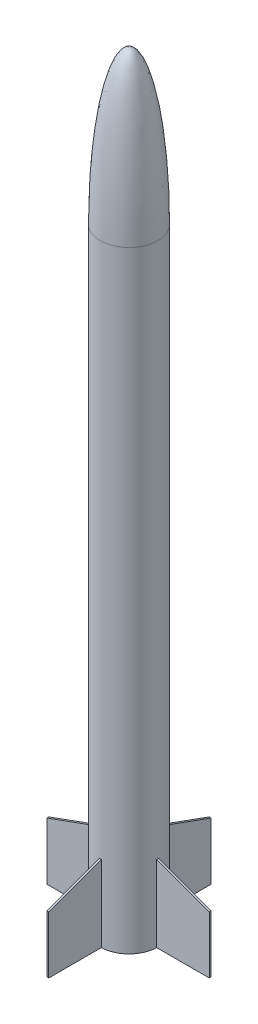
SolidWorks part; units mm, degrees
ref_plane "Front Plane" through (0, 0, 0) normal (0, 0, 1) x (1, 0, 0)
ref_plane "Top Plane" through (0, 0, 0) normal (0, 1, 0) x (1, 0, 0)
ref_plane "Right Plane" through (0, 0, 0) normal (1, 0, 0) x (0, 0, -1)
sketch "Sketch1" plane through (0, 0, 0) normal (0, 0, 1) x (1, 0, 0)
  line L0 (75, 0) -> (75, 1600)
  line L1 (0, 0) -> (0, 2000) construction
  line L2 (65, 0) -> (65, 1600)
  line L3 (0, 1990) -> (0, 2000)
  line L4 (65, 0) -> (75, 0)
  ellipse E0 centre (0, 1600) end of major axis (0, 2000) minor radius 75 (75, 1600) -> (0, 2000) ccw
  spline S0 degree 1 poles (65, 1600) (0, 1990) knots 0 0 1 1 construction
  spline S1 degree 3 poles (65, 1600) (65, 1613.008) (64.76, 1639.0954) (63.6835, 1677.7875) (61.9012, 1715.7351) (58.6084, 1764.8191) (52.8332, 1822.4383) (45.0808, 1872.7908) (37.9007, 1907.4884) (32.0956, 1930.4423) (25.9549, 1950.0586) (19.5957, 1966.0734) (13.2092, 1978.2156) (8.1667, 1984.8479) (4.7233, 1987.9953) (2.6031, 1989.3526) (1.3254, 1989.8256) (0.5303, 1989.9775) (0.1812, 1990) (0, 1990) knots -1.570796 -1.570796 -1.570796 -1.570796 -1.472622 -1.374447 -1.276272 -1.178097 -0.981748 -0.785398 -0.687223 -0.589049 -0.490874 -0.392699 -0.294524 -0.19635 -0.147262 -0.098175 -0.049087 -0.024544 0 0 0 0
  dimension "D1" = 75
  dimension "D2" = 1600
  dimension "D3" = 2000
  dimension "D4" = 10
revolve "Body & Nose cone" add sketch "Sketch1" angle 360 about L1
sketch "Sketch2" plane through (0, 0, 0) normal (0, 0, 1) x (1, 0, 0)
  line L0 (65, 1600) -> (-65, 1600) construction
  line L1 (0, 0) -> (0, 1750) construction
  line L2 (0, 1750) -> (59.5, 1750)
  line L3 (59.5, 1750) -> (59.5, 1450)
  line L4 (59.5, 1450) -> (0, 1450)
  line L5 (0, 1750) -> (0, 1450)
  point P4 (0, 0)
  dimension "D1" = 300
  dimension "D2" = 150
  dimension "D3" = 59.5
revolve "Tube Coupler" add sketch "Sketch2" angle 360 about L1
sketch "Sketch3" plane through (0, 0, 0) normal (0, 0, 1) x (1, 0, 0)
  line L0 (75, 0) -> (212.3739, 0)
  line L1 (212.3739, 0) -> (212.3739, 150)
  line L2 (212.3739, 150) -> (75, 200)
  line L3 (75, 0) -> (75, 1600) construction
  line L5 (75, 200) -> (229.0239, 200) construction
  line L16 (75, 200) -> (75, 150.9)
  line L17 (75, 150.9) -> (70, 150.9)
  line L18 (70, 150.9) -> (70, 15.9)
  line L19 (70, 15.9) -> (75, 15.9)
  line L20 (75, 15.9) -> (75, 0)
  dimension "D1" = 200
  dimension "D2" = 150
  dimension "D3" = 20
  dimension "D4" = 49.1
  dimension "D5" = 135
  dimension "D6" = 5
extrude "Fin" add sketch "Sketch3" against normal blind 2.5 and the other way blind 2.5 separate body
pattern_circular "CirPattern1" count 4 over 360 about axis through (0, 0, 0) along (0, -1, 0) reverse direction yes of bodies 104
